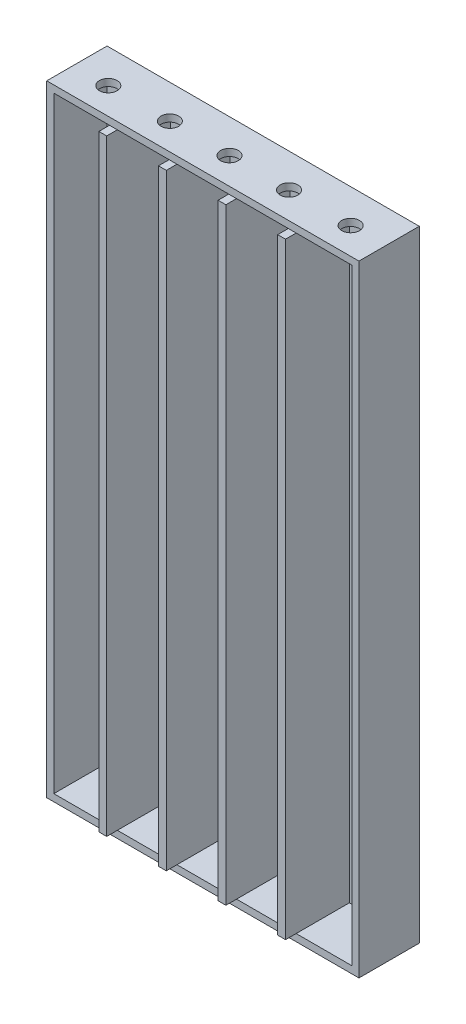
SolidWorks part; units mm, degrees
ref_plane "Front Plane" through (0, 0, 0) normal (0, 0, 1) x (1, 0, 0)
ref_plane "Top Plane" through (0, 0, 0) normal (0, 1, 0) x (1, 0, 0)
ref_plane "Right Plane" through (0, 0, 0) normal (1, 0, 0) x (0, 0, -1)
ref_plane "Plane1" through (0, 10, 0) normal (0, 1, 0) x (1, 0, 0)
sketch "Sketch1" plane through (0, 0, 0) normal (0, 0, 1) x (1, 0, 0)
  line L1 (-44, -87.5) -> (44, -87.5)
  line L2 (-44, -87.5) -> (-44, 87.5)
  line L3 (-44, 87.5) -> (44, 87.5)
  line L4 (44, -87.5) -> (44, 87.5)
  line L5 (-44, -87.5) -> (44, 87.5) construction
  line L6 (-44, 87.5) -> (44, -87.5) construction
  point P0 (0, 0)
  dimension "D1" = 88
  dimension "D2" = 175
extrude "Boss-Extrude1" add sketch "Sketch1" along normal blind 2
sketch "Sketch2" plane through (0, 0, 2) normal (0, 0, 1) x (1, 0, 0)
  line L4 (44, -87.5) -> (44, 87.5)
  line L5 (44, 87.5) -> (-44, 87.5)
  line L6 (-44, 87.5) -> (-44, -87.5)
  line L7 (-44, -87.5) -> (44, -87.5)
  line L8 (44, -87.5) -> (44, 87.5)
  line L9 (44, 87.5) -> (-44, 87.5)
  line L10 (-44, 87.5) -> (-44, -87.5)
  line L11 (-44, -87.5) -> (44, -87.5)
  dimension "D1" = 0
extrude "Extrude-Thin1" add sketch "Sketch2" along normal blind 15 thin thin type one direction reverse wall 2
sketch "Sketch7" plane through (0, 10, 0) normal (0, -1, 0) x (1, 0, 0)
  line L10 (-42.3768, -2.407) -> (42.5401, -2.407)
  line L11 (47.6224, 2.5172) -> (47.6224, 16.4468)
  line L12 (41.5429, 22.3538) -> (17.5198, 22.3437)
  line L13 (17.5198, 22.3437) -> (-42.3262, 22.3337)
  line L14 (-47.3776, 17.3465) -> (-47.3776, 2.5515)
  spline S8 degree 3 poles (42.5401, -2.407) (42.8706, -2.4078) (43.196, -2.3778) (43.8369, -2.2583) (44.1553, -2.1674) (44.7669, -1.9274) (45.0576, -1.7798) (45.6085, -1.4299) (45.8711, -1.2247) (46.3442, -0.773) (46.5566, -0.526) (46.8382, -0.1231) (46.9263, 0.0175) (47.0866, 0.3047) (47.159, 0.4514) (47.3532, 0.9003) (47.4524, 1.2115) (47.5875, 1.8587) (47.6216, 2.1864) (47.6224, 2.5172) knots 0 0 0 0 0.125 0.125 0.25 0.25 0.375 0.375 0.5 0.5 0.625 0.625 0.6875 0.6875 0.75 0.75 0.875 0.875 1 1 1 1
  spline S9 degree 3 poles (47.6224, 16.4468) (47.6224, 16.843) (47.5828, 17.2324) (47.4656, 17.8067) (47.4168, 17.9965) (47.2994, 18.3728) (47.2305, 18.5591) (46.9987, 19.1005) (46.8095, 19.4421) (46.474, 19.926) (46.3528, 20.0833) (46.0967, 20.383) (45.962, 20.5254) (45.5387, 20.9312) (45.2308, 21.1731) (44.563, 21.5988) (44.2136, 21.7758) (43.4861, 22.0621) (43.1044, 22.1719) (42.3303, 22.3175) (41.9388, 22.3539) (41.5429, 22.3538) knots 0 0 0 0 0.125 0.125 0.1875 0.1875 0.25 0.25 0.375 0.375 0.4375 0.4375 0.5 0.5 0.625 0.625 0.75 0.75 0.875 0.875 1 1 1 1
  spline S10 degree 3 poles (-42.3262, 22.3337) (-42.6576, 22.3345) (-42.9836, 22.3031) (-43.4649, 22.2099) (-43.624, 22.171) (-43.9396, 22.0774) (-44.0966, 22.0224) (-44.5538, 21.8366) (-44.8431, 21.6848) (-45.3911, 21.3255) (-45.6513, 21.1158) (-46.1184, 20.6569) (-46.3281, 20.4063) (-46.6064, 19.998) (-46.6931, 19.856) (-46.8504, 19.5673) (-46.9214, 19.4199) (-47.1124, 18.9685) (-47.2104, 18.6543) (-47.3432, 18.0058) (-47.3769, 17.678) (-47.3776, 17.3465) knots 0 0 0 0 0.125 0.125 0.1875 0.1875 0.25 0.25 0.375 0.375 0.5 0.5 0.625 0.625 0.6875 0.6875 0.75 0.75 0.875 0.875 1 1 1 1
  spline S11 degree 3 poles (-47.3776, 2.5515) (-47.3776, 2.223) (-47.3453, 1.9) (-47.25, 1.4233) (-47.2104, 1.2658) (-47.1151, 0.9534) (-47.0592, 0.7983) (-46.8708, 0.3471) (-46.717, 0.0618) (-46.3535, -0.4777) (-46.142, -0.7328) (-45.6803, -1.1896) (-45.4283, -1.3943) (-44.8814, -1.7557) (-44.5911, -1.9086) (-43.9903, -2.1544) (-43.6758, -2.2489) (-43.0316, -2.3754) (-42.706, -2.407) (-42.3768, -2.407) knots 0 0 0 0 0.125 0.125 0.1875 0.1875 0.25 0.25 0.375 0.375 0.5 0.5 0.625 0.625 0.75 0.75 0.875 0.875 1 1 1 1
sketch "Sketch10" plane through (0, 0, 2) normal (0, 0, -1) x (-1, 0, 0)
  line L8 (42, -85.5) -> (42, 85.5)
  line L9 (-42, -85.5) -> (42, -85.5)
  line L10 (-42, 85.5) -> (-42, -85.5)
  line L11 (42, 85.5) -> (-42, 85.5)
extrude "Cut-Extrude2" cut sketch "Sketch10" against normal blind 18 rebuild error yes
sketch "Sketch3" plane through (0, 0, 2) normal (0, 0, 1) x (1, 0, 0)
  line L0 (-25.2, 85.5) -> (-25.2, -85.5)
  line L1 (42, 85.5) -> (-42, 85.5) construction
  line L3 (-8.4, 85.5) -> (-8.4, -85.5)
  line L4 (42, 85.5) -> (-42, 85.5) construction
  line L5 (25.2, 85.5) -> (25.2, -85.5)
  line L6 (8.4, 85.5) -> (8.4, -85.5)
  line L8 (-42, 85.5) -> (-42, -85.5) construction
  line L9 (42, -85.5) -> (42, 85.5) construction
  line L11 (42, -85.5) -> (-42, -85.5) construction
  dimension "D1" = 16.8
  dimension "D2" = 16.8
  dimension "D3" = 16.8
  dimension "D4" = 16.8
  dimension "D5" = 16.8
extrude "Extrude-Thin2" add sketch "Sketch3" along normal blind 18 thin thin type mid plane wall 2.2
sketch "Sketch4" plane through (0, 87.5, 0) normal (0, 1, 0) x (1, 0, 0)
  line L0 (26.3, -17) -> (26.3, -2) construction
  line L1 (26.3, -2) -> (42, -2) construction
  line L2 (42, -2) -> (42, -17) construction
  line L3 (42, -17) -> (26.3, -17) construction
  line L4 (9.5, -17) -> (9.5, -2) construction
  line L5 (9.5, -2) -> (24.1, -2) construction
  line L6 (24.1, -2) -> (24.1, -17) construction
  line L7 (24.1, -17) -> (9.5, -17) construction
  line L8 (-7.3, -2) -> (7.3, -2) construction
  line L9 (7.3, -2) -> (7.3, -17) construction
  line L10 (7.3, -17) -> (-7.3, -17) construction
  line L11 (-7.3, -17) -> (-7.3, -2) construction
  line L12 (-24.1, -2) -> (-9.5, -2) construction
  line L13 (-9.5, -2) -> (-9.5, -17) construction
  line L14 (-9.5, -17) -> (-24.1, -17) construction
  line L15 (-24.1, -17) -> (-24.1, -2) construction
  line L16 (-42, -2) -> (-26.3, -2) construction
  line L17 (-26.3, -2) -> (-26.3, -17) construction
  line L18 (-26.3, -17) -> (-42, -17) construction
  line L19 (-42, -17) -> (-42, -2) construction
  line L20 (26.3, -17) -> (26.3, -2) construction
  line L21 (26.3, -2) -> (42, -2) construction
  line L22 (42, -2) -> (42, -17) construction
  line L23 (42, -17) -> (26.3, -17) construction
  line L24 (9.5, -17) -> (9.5, -2) construction
  line L25 (9.5, -2) -> (24.1, -2) construction
  line L26 (24.1, -2) -> (24.1, -17) construction
  line L27 (24.1, -17) -> (9.5, -17) construction
  line L28 (-7.3, -2) -> (7.3, -2) construction
  line L29 (7.3, -2) -> (7.3, -17) construction
  line L30 (7.3, -17) -> (-7.3, -17) construction
  line L31 (-7.3, -17) -> (-7.3, -2) construction
  line L32 (-24.1, -2) -> (-9.5, -2) construction
  line L33 (-9.5, -2) -> (-9.5, -17) construction
  line L34 (-9.5, -17) -> (-24.1, -17) construction
  line L35 (-24.1, -17) -> (-24.1, -2) construction
  line L36 (-42, -2) -> (-26.3, -2) construction
  line L37 (-26.3, -2) -> (-26.3, -17) construction
  line L38 (-26.3, -17) -> (-42, -17) construction
  line L39 (-42, -17) -> (-42, -2) construction
  line L40 (42, -9.5) -> (-42, -9.5) construction
  line L41 (-16.8, -17) -> (-16.8, -2) construction
  line L42 (-34.15, -17) -> (-34.15, -2) construction
  line L43 (0, -17) -> (0, -2) construction
  line L44 (16.8, -17) -> (16.8, -2) construction
  line L45 (34.15, -17) -> (34.15, -2) construction
  point P26 (34.15, -9.5)
  point P28 (16.8, -9.5)
  point P30 (0, -9.5)
  point P31 (-16.8, -9.5)
  point P34 (-34.15, -9.5)
hole_wizard "Ø5.0mm Dowel Hole3" positions "Sketch5" profile "Sketch6" hole size "Ø5.0" standard "BSI" end condition up to next
sketch "Sketch5" plane through (0, 87.5, 0) normal (0, 1, 0) x (1, 0, 0)
  line L0 (-34.15, -17) -> (-34.15, -2) construction
  line L1 (-16.8, -17) -> (-16.8, -2) construction
  point P0 (-34.15, -9.5)
  point P4 (-16.8, -9.5)
  point P8 (0, -9.5)
  point P11 (16.8, -9.5)
  point P14 (34.15, -9.5)
sketch "Sketch6" plane through (-34.15, 87.5, 9.5) normal (1, 0, 0) x (0, 0, 1)
  line L0 (0, 0) -> (0, 2)
  line L1 (0, 2) -> (2.5, 2)
  line L2 (2.5, 2) -> (2.5, 0)
  line L5 (2.5, 0) -> (0, 0)
  line L11 (0, -6.35) -> (0, 107.95) construction
  dimension "Thru Hole Dia." = 5
  dimension "Thru Hole Depth" = 2
sketch "Sketch11" plane through (0, -87.5, 0) normal (0, -1, 0) x (1, 0, 0)
  line L0 (-37, 9.5) -> (37, 9.5) construction
  line L1 (42, 9.5) -> (-42, 9.5) construction
  line L2 (-37, 27.5) -> (37, 27.5)
  line L3 (-37, -8.5) -> (37, -8.5)
  arc A0 (-37, 27.5) -> (-37, -8.5) centre (-37, 9.5) ccw
  arc A1 (37, -8.5) -> (37, 27.5) centre (37, 9.5) ccw
  point P4 (0, 9.5)
  point P9 (37.1573, 9.5)
  point P10 (-38.8314, 9.5)
  point P11 (40.074, 9.5)
  point P12 (-42, 9.5)
  point P14 (42, 9.5)
  point P16 (0, 0)
  point P17 (-42, 9.5)
  point P18 (-42, 9.5)
  point P19 (-37.5265, 9.5)
  point P20 (42, 9.5)
  point P21 (35.6221, 9.5)
  dimension "D1" = 18
  dimension "D2" = 5
  dimension "D3" = 5
